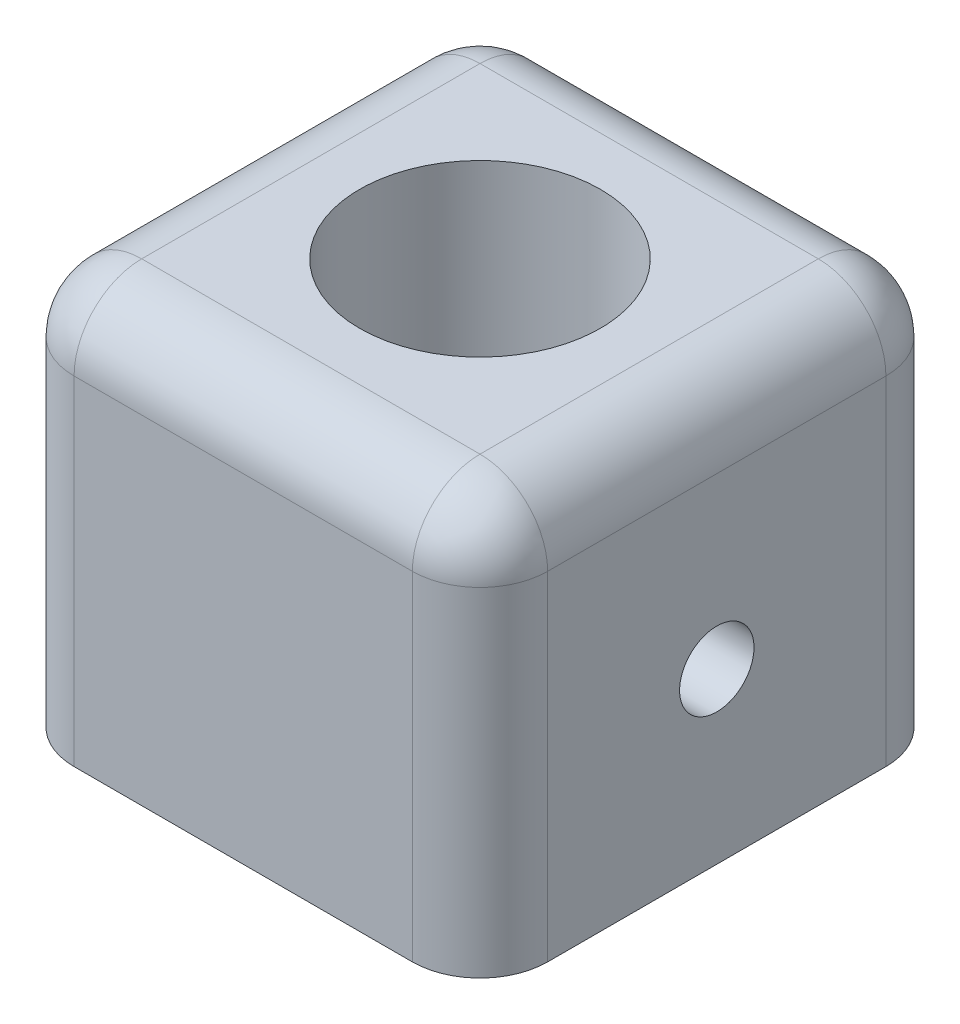
SolidWorks part; units mm, degrees
ref_plane "Front Plane" through (0, 0, 0) normal (0, 0, 1) x (1, 0, 0)
ref_plane "Top Plane" through (0, 0, 0) normal (0, 1, 0) x (1, 0, 0)
ref_plane "Right Plane" through (0, 0, 0) normal (1, 0, 0) x (0, 0, -1)
sketch "Sketch1" plane through (0, 0, 0) normal (0, 1, 0) x (1, 0, 0)
  line L1 (0, 0) -> (35, 0)
  line L2 (0, 0) -> (0, 35)
  line L3 (0, 35) -> (35, 35)
  line L4 (35, 0) -> (35, 35)
  dimension "D1" = 35
extrude "Boss-Extrude1" add sketch "Sketch1" along normal blind 30
sketch "Sketch2" plane through (0, 0, 0) normal (0, -1, 0) x (1, 0, 0)
  line L0 (0, -17.5) -> (35, -17.5) construction
  line L1 (0, -35) -> (0, 0) construction
  line L2 (35, 0) -> (35, -35) construction
  line L3 (17.5, 0) -> (17.5, -35) construction
  line L4 (0, 0) -> (35, 0) construction
  line L5 (35, -35) -> (0, -35) construction
  line L7 (7.5, -27.5) -> (27.5, -27.5)
  line L8 (7.5, -27.5) -> (7.5, -7.5)
  line L9 (7.5, -7.5) -> (27.5, -7.5)
  line L10 (27.5, -27.5) -> (27.5, -7.5)
  line L11 (7.5, -27.5) -> (27.5, -7.5) construction
  line L12 (7.5, -7.5) -> (27.5, -27.5) construction
  point P6 (17.5, -17.5)
  point P7 (17.5, -17.5)
  dimension "D2" = 20
extrude "Cut-Extrude1" cut sketch "Sketch2" against normal blind 15
sketch "Sketch3" plane through (0, 30, 0) normal (0, 1, 0) x (1, 0, 0)
  line L0 (0, 17.5) -> (35, 17.5) construction
  line L1 (0, 35) -> (0, 0) construction
  line L2 (35, 0) -> (35, 35) construction
  line L3 (17.5, 35) -> (17.5, 0) construction
  line L4 (35, 35) -> (0, 35) construction
  line L5 (0, 0) -> (35, 0) construction
  circle A0 centre (17.5, 17.5) radius 8.9
  point P14 (12.5, 12.5)
  dimension "D1" = 17.8
extrude "Cut-Extrude2" cut sketch "Sketch3" against normal through all
hole_wizard "CBORE for M2 SHCS1" positions "3DSketch1" profile "Sketch5" counterbore size "M2" standard "ANSI Metric" end condition up to next
sketch3d "3DSketch1"
  line L0 (35, 0, -17.5) -> (35, 30, -17.5) construction
  line L1 (35, 0, 0) -> (35, 0, -35) construction
  line L2 (35, 30, 0) -> (35, 30, -35) construction
  point P0 (35, 12.5, -17.5)
  dimension "D1" = 17.5
sketch "Sketch5" plane through (35, 12.5, -17.5) normal (0, 1, 0) x (0, 0, -1)
  line L0 (0, 0) -> (0, 7.5)
  line L1 (0, 7.5) -> (1.3, 7.5)
  line L3 (1.3, 7.5) -> (1.3, 6)
  line L4 (1.3, 6) -> (2.75, 6)
  line L5 (2.75, 6) -> (2.75, 0)
  line L7 (2.75, 0) -> (0, 0)
  line L11 (0, -6.35) -> (0, 107.95) construction
  dimension "Thru Hole Dia." = 2.6
  dimension "Thru Hole Depth" = 7.5
  dimension "C'Bore Dia." = 5.5
  dimension "C'Bore Depth" = 6
hole_wizard "CBORE for M2 SHCS2" positions "3DSketch2" profile "Sketch6" counterbore size "M2" standard "ANSI Metric" end condition up to next
sketch3d "3DSketch2"
  line L0 (0, 0, -17.5) -> (0, 30, -17.5) construction
  line L1 (0, 0, -35) -> (0, 0, 0) construction
  line L2 (0, 30, -35) -> (0, 30, 0) construction
  point P0 (0, 12.5, -17.5)
  dimension "D1" = 17.5
sketch "Sketch6" plane through (0, 12.5, -17.5) normal (0, 1, 0) x (0, 0, 1)
  line L0 (0, 0) -> (0, 7.5)
  line L1 (0, 7.5) -> (1.3, 7.5)
  line L3 (1.3, 7.5) -> (1.3, 6)
  line L4 (1.3, 6) -> (2.75, 6)
  line L5 (2.75, 6) -> (2.75, 0)
  line L7 (2.75, 0) -> (0, 0)
  line L11 (0, -6.35) -> (0, 107.95) construction
  dimension "Thru Hole Dia." = 2.6
  dimension "Thru Hole Depth" = 7.5
  dimension "C'Bore Dia." = 5.5
  dimension "C'Bore Depth" = 6
fillet "Fillet1" radius 5 4 edges at (0, 30, -17.5) (17.5, 30, -35) (35, 30, -17.5) (17.5, 30, 0)
fillet "Fillet2" radius 5 8 edges at (1.4645, 28.5355, -33.5355) (33.5355, 28.5355, -33.5355) (33.5355, 28.5355, -1.4645) (1.4645, 28.5355, -1.4645) (0, 12.5, -35) (35, 12.5, -35) (35, 12.5, 0) (0, 12.5, 0)
hole_wizard "M3x0.5 Tapped Hole1" positions "3DSketch4" profile "Sketch8" tap size "M3x0.5" standard "ANSI Metric"
sketch3d "3DSketch4"
  line L8 (35, 0, -17.5) -> (27.5, 0, -17.5)
  line L9 (35, 0, -5) -> (35, 0, -30) construction
  line L10 (27.5, 0, -27.5) -> (27.5, 0, -7.5) construction
  line L12 (17.5, 0, -27.5) -> (17.5, 0, -35)
  line L13 (7.5, 0, -27.5) -> (27.5, 0, -27.5) construction
  line L14 (30, 0, -35) -> (5, 0, -35) construction
  line L16 (7.5, 0, -17.5) -> (0, 0, -17.5)
  line L17 (7.5, 0, -7.5) -> (7.5, 0, -27.5) construction
  line L18 (0, 0, -30) -> (0, 0, -5) construction
  line L20 (17.5, 0, -7.5) -> (17.5, 0, 0)
  line L21 (27.5, 0, -7.5) -> (7.5, 0, -7.5) construction
  line L22 (5, 0, 0) -> (30, 0, 0) construction
  point P0 (17.5, 0, -31.25)
  point P2 (3.75, 0, -17.5)
  point P4 (17.5, 0, -3.75)
  point P6 (31.25, 0, -17.5)
  point P55 (12.5, 0, -2.545)
  point P56 (23.1541, 0, -12.5)
  point P57 (1.904, 0, -12.5)
  point P58 (12.5, 0, -22.8068)
  point P59 (0, 0, 0)
  point P60 (0, 0, 0)
sketch "Sketch8" plane through (17.5, 0, -31.25) normal (1, 0, 0) x (0, 0, -1)
  line L0 (0, 0) -> (0, 5.7511)
  line L1 (0, 5.7511) -> (1.25, 5)
  line L2 (1.25, 5) -> (1.25, 0)
  line L5 (1.25, 0) -> (0, 0)
  line L10 (0, 5.7511) -> (-1.25, 5) construction
  line L11 (0, -6.35) -> (0, 107.95) construction
  dimension "Tap Drill Dia." = 2.5
  dimension "Tap Drill Depth" = 5
  dimension "Drill Angle" = 118
cosmetic thread "Hole Thread1" parameters "D1"=6, "D2"=3
cosmetic thread "Hole Thread2" parameters "D1"=6, "D2"=3
cosmetic thread "Hole Thread3" parameters "D1"=6, "D2"=3
cosmetic thread "Hole Thread4" parameters "D1"=6, "D2"=3
